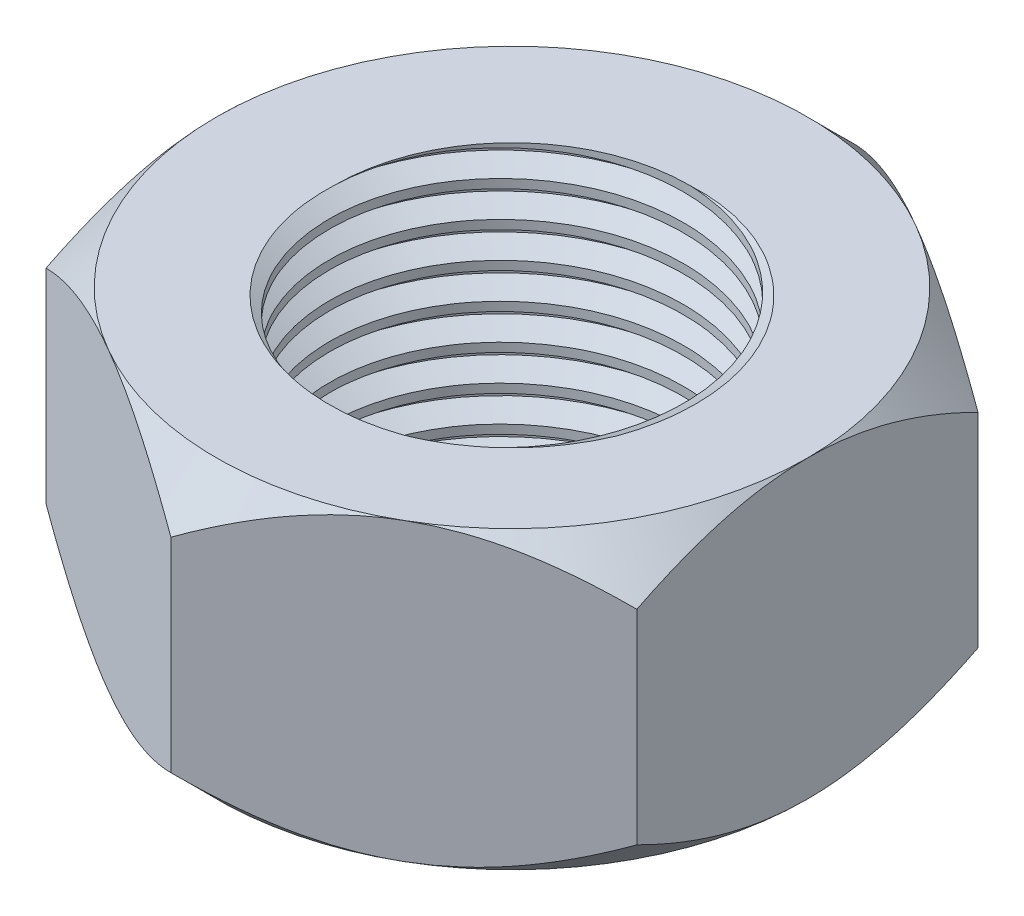
SolidWorks part; units mm, degrees
material "Cast Stainless Steel"
ref_plane "Front Plane" through (0, 0, 0) normal (0, 0, 1) x (1, 0, 0)
ref_plane "Top Plane" through (0, 0, 0) normal (0, 1, 0) x (1, 0, 0)
ref_plane "Right Plane" through (0, 0, 0) normal (1, 0, 0) x (0, 0, -1)
sketch "Sketch1" plane through (0, 0, 0) normal (0, 1, 0) x (1, 0, 0)
  line L1 (0, 4.8113) -> (-4.1667, 2.4056)
  line L2 (-4.1667, 2.4056) -> (-4.1667, -2.4056)
  line L3 (-4.1667, -2.4056) -> (0, -4.8113)
  line L4 (0, -4.8113) -> (4.1667, -2.4056)
  line L5 (4.1667, -2.4056) -> (4.1667, 2.4056)
  line L6 (4.1667, 2.4056) -> (0, 4.8113)
  circle A0 centre (0, 0) radius 2.5
  circle A1 centre (0, 0) radius 4.1667 construction
  dimension "D1" = 5
  dimension "D2" = 8.3333
extrude "Boss-Extrude1" add sketch "Sketch1" along normal mid plane 4.1667
sketch "Sketch3" plane through (0, 2.0833, 0) normal (0, 1, 0) x (1, 0, 0)
  line L0 (4.1667, 2.4056) -> (0, 4.8113) construction
  circle A0 centre (0, 0) radius 4.1667
extrude "Cut-Extrude5" cut sketch "Sketch3" against normal blind 2.5 draft 45 flip side to cut
mirror "Mirror1" about plane through (0, 0, 0) normal (0, 1, 0) of "Cut-Extrude5"
thread "Thread1" pitch 0.5 method cut profile "Thread Profile1" start angle 0, offset 5, length 10, pitch 0.5, diameter 5
ref_plane "Plane1" through (-2.5, 7.0833, 0) normal (0, 0, 1) x (-1, 0, 0)
sketch "Thread Profile1" plane through (-2.5, 7.0833, 0) normal (0, 0, 1) x (-1, 0, 0)
  line L0 (0, 0) -> (0, 0.5) construction
  line L1 (0, 0) -> (0.2706, 0.1562)
  line L2 (0.2706, 0.1562) -> (0.2706, 0.2187)
  line L3 (0.2706, 0.2187) -> (0, 0.375)
  line L4 (0.2706, 0.1875) -> (0, 0.1875) construction
  line L11 (0, 0) -> (0, 0.375)
  point P2 (0, 0)
  dimension "Pitch" = 0.5
  dimension "Profile_Angle" = 60
  dimension "Profile_Land" = 0.0625
  dimension "Profile_Height" = 0.2706
